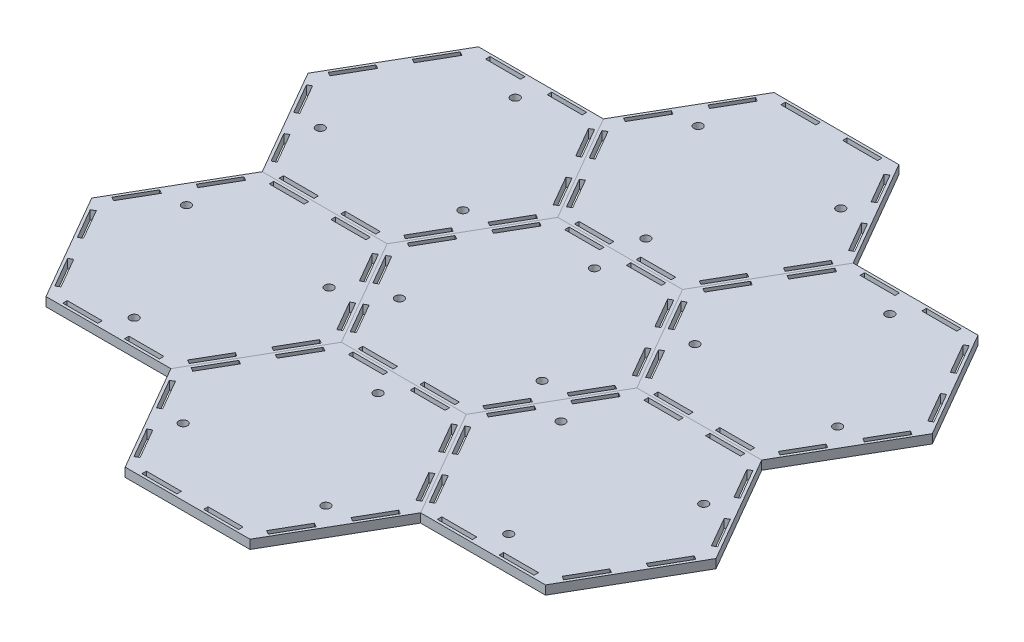
SolidWorks part; units mm, degrees
material "Cedar"
ref_plane "Front Plane" through (0, 0, 0) normal (0, 0, 1) x (1, 0, 0)
ref_plane "Top Plane" through (0, 0, 0) normal (0, 1, 0) x (1, 0, 0)
ref_plane "Right Plane" through (0, 0, 0) normal (1, 0, 0) x (0, 0, -1)
sketch "Sketch1" plane through (0, 0, 0) normal (0, 1, 0) x (1, 0, 0)
  line L0 (-88.9, 0) -> (-44.45, -76.9897)
  line L1 (88.9, 0) -> (44.45, 76.9897)
  line L2 (44.45, 76.9897) -> (-44.45, 76.9897)
  line L3 (-44.45, 76.9897) -> (-88.9, 0)
  line L4 (-44.45, -76.9897) -> (44.45, -76.9897)
  line L5 (44.45, -76.9897) -> (88.9, 0)
  line L6 (0, 0) -> (88.9, 0) construction
  circle A0 centre (0, 0) radius 76.9897 construction
  dimension "D1" = 88.9
extrude "Boss-Extrude1" add sketch "Sketch1" along normal blind 6.35
sketch "Sketch2" plane through (0, 6.35, 0) normal (0, 1, 0) x (1, 0, 0)
  line L0 (0, 0) -> (0, 58.6588) construction
  line L1 (50.8, -29.3294) -> (0, 58.6588) construction
  line L2 (0, 58.6588) -> (-50.8, -29.3294) construction
  line L3 (-50.8, -29.3294) -> (50.8, -29.3294) construction
  line L4 (-85.9671, 5.08) -> (-38.5841, -76.9897) construction
  line L5 (-44.45, 76.9897) -> (-88.9, 0) construction
  line L6 (-44.45, -76.9897) -> (44.45, -76.9897) construction
  line L7 (-88.9, 0) -> (-44.45, -76.9897) construction
  line L8 (-66.675, -38.4948) -> (-62.2756, -35.9548) construction
  line L9 (-79.4841, -6.1488) -> (-82.2337, -7.7363)
  line L10 (-82.2337, -7.7363) -> (-69.7877, -29.2934)
  line L11 (-69.7877, -29.2934) -> (-67.0381, -27.7059)
  line L12 (-67.0381, -27.7059) -> (-79.4841, -6.1488)
  line L13 (-45.0671, -65.7608) -> (-47.8167, -67.3483)
  line L14 (-57.5131, -44.2037) -> (-45.0671, -65.7608)
  line L15 (-47.8167, -67.3483) -> (-60.2627, -45.7912)
  line L16 (-60.2627, -45.7912) -> (-57.5131, -44.2037)
  line L17 (-38.5841, 76.9897) -> (-85.9671, -5.08) construction
  line L18 (-45.0671, 65.7608) -> (-47.8167, 67.3483)
  line L19 (-47.8167, 67.3483) -> (-60.2627, 45.7912)
  line L20 (-57.5131, 44.2037) -> (-45.0671, 65.7608)
  line L21 (-60.2627, 45.7912) -> (-57.5131, 44.2037)
  line L22 (-66.675, 38.4948) -> (-62.2756, 35.9548) construction
  line L23 (-69.7877, 29.2934) -> (-67.0381, 27.7059)
  line L24 (-82.2337, 7.7363) -> (-69.7877, 29.2934)
  line L25 (-67.0381, 27.7059) -> (-79.4841, 6.1488)
  line L26 (-79.4841, 6.1488) -> (-82.2337, 7.7363)
  line L27 (47.3829, 71.9097) -> (-47.3829, 71.9097) construction
  line L28 (34.417, 71.9097) -> (34.417, 75.0847)
  line L29 (34.417, 75.0847) -> (9.525, 75.0847)
  line L30 (9.525, 71.9097) -> (34.417, 71.9097)
  line L31 (9.525, 75.0847) -> (9.525, 71.9097)
  line L32 (0, 76.9897) -> (0, 71.9097) construction
  line L33 (-9.525, 75.0847) -> (-9.525, 71.9097)
  line L34 (-34.417, 75.0847) -> (-9.525, 75.0847)
  line L35 (-9.525, 71.9097) -> (-34.417, 71.9097)
  line L36 (-34.417, 71.9097) -> (-34.417, 75.0847)
  line L37 (85.9671, -5.08) -> (38.5841, 76.9897) construction
  line L38 (79.4841, 6.1488) -> (82.2337, 7.7363)
  line L39 (82.2337, 7.7363) -> (69.7877, 29.2934)
  line L40 (67.0381, 27.7059) -> (79.4841, 6.1488)
  line L41 (69.7877, 29.2934) -> (67.0381, 27.7059)
  line L42 (66.675, 38.4948) -> (62.2756, 35.9548) construction
  line L43 (60.2627, 45.7912) -> (57.5131, 44.2037)
  line L44 (47.8167, 67.3483) -> (60.2627, 45.7912)
  line L45 (57.5131, 44.2037) -> (45.0671, 65.7608)
  line L46 (45.0671, 65.7608) -> (47.8167, 67.3483)
  line L47 (38.5841, -76.9897) -> (85.9671, 5.08) construction
  line L48 (45.0671, -65.7608) -> (47.8167, -67.3483)
  line L49 (47.8167, -67.3483) -> (60.2627, -45.7912)
  line L50 (57.5131, -44.2037) -> (45.0671, -65.7608)
  line L51 (60.2627, -45.7912) -> (57.5131, -44.2037)
  line L52 (66.675, -38.4948) -> (62.2756, -35.9548) construction
  line L53 (69.7877, -29.2934) -> (67.0381, -27.7059)
  line L54 (82.2337, -7.7363) -> (69.7877, -29.2934)
  line L55 (67.0381, -27.7059) -> (79.4841, -6.1488)
  line L56 (79.4841, -6.1488) -> (82.2337, -7.7363)
  line L57 (-47.3829, -71.9097) -> (47.3829, -71.9097) construction
  line L58 (-34.417, -71.9097) -> (-34.417, -75.0847)
  line L59 (-34.417, -75.0847) -> (-9.525, -75.0847)
  line L60 (-9.525, -71.9097) -> (-34.417, -71.9097)
  line L61 (-9.525, -75.0847) -> (-9.525, -71.9097)
  line L62 (0, -76.9897) -> (0, -71.9097) construction
  line L63 (9.525, -75.0847) -> (9.525, -71.9097)
  line L64 (34.417, -75.0847) -> (9.525, -75.0847)
  line L65 (9.525, -71.9097) -> (34.417, -71.9097)
  line L66 (34.417, -71.9097) -> (34.417, -75.0847)
  circle A0 centre (0, 0) radius 29.3294 construction
  circle A1 centre (-50.8, -29.3294) radius 3.0734
  circle A4 centre (0, 58.6588) radius 3.0734
  circle A5 centre (50.8, -29.3294) radius 3.0734
  point P13 (0, 0)
  point P92 (0, 0)
  point P94 (0, 0)
  dimension "D2" = 6.1468
  dimension "D3" = 3
  dimension "D1" = 101.6
  dimension "D4" = 5.08
  dimension "D5" = 3.175
  dimension "D6" = 24.892
  dimension "D7" = 9.525
  dimension "D8" = 6
extrude "Cut-Extrude1" cut sketch "Sketch2" against normal through all
ref_axis "Axis2" through (0, 0, 0) along (0, 1, 0)
mirror "Mirror1" about plane through (44.45, 6.35, 76.9897) normal (-0.866, 0, -0.5) of bodies 102
pattern_circular "CirPattern1" count 6 over 360 about axis through (0, 0, 0) along (0, 1, 0) of bodies 103
